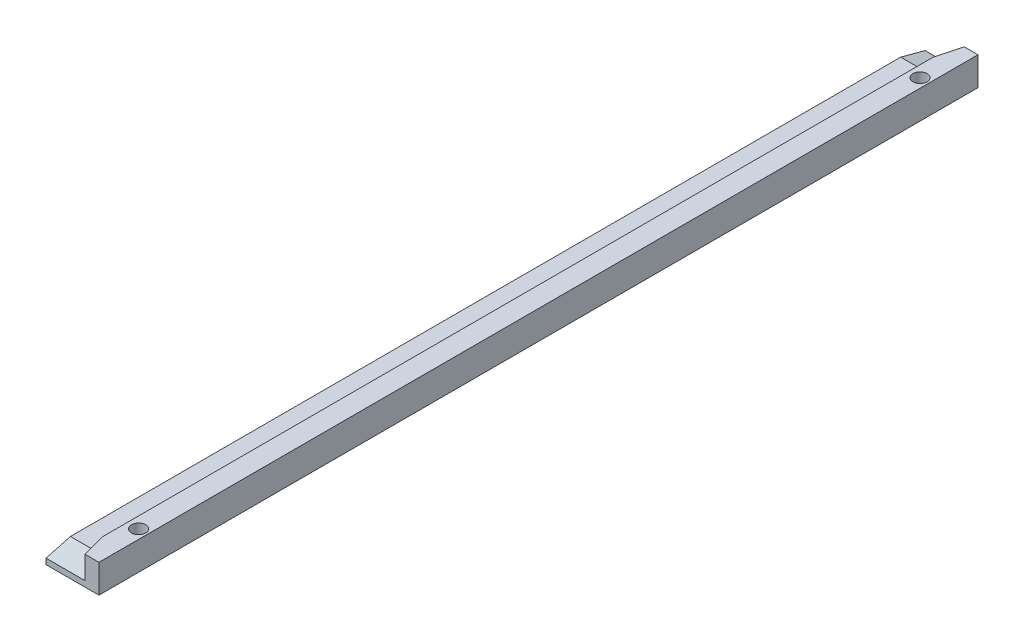
SolidWorks part; units mm, degrees
note: '?' marks a value the reader was unsure of.
material "6061 Alloy"
ref_plane "Front" through (0, 0, 0) normal (0, 0, 1) x (1, 0, 0)
ref_plane "Top" through (0, 0, 0) normal (0, 1, 0) x (1, 0, 0)
ref_plane "Right" through (0, 0, 0) normal (1, 0, 0) x (0, 0, -1)
ref_axis "X" through (-80.9, 0, 0) along (1, 0, 0)?
ref_axis "Y" through (0, 0, -80.9) along (0, 0, 1)?
ref_axis "Z" through (0, 50, 0) along (0, -1, 0)?
sketch "Sketch1" plane through (0, 0, 0) normal (0, 0, 1) x (1, 0, 0)
  line L0 (0, 0) -> (0, 22.225)
  line L1 (0, 0) -> (-28.448, 0)
  line L2 (-41.275, 9.525) -> (-15.875, 9.525)
  line L4 (-15.875, 9.525) -> (-15.875, 22.225)
  line L5 (-15.875, 22.225) -> (0, 22.225)
  line L7 (-41.275, 9.525) -> (-41.275, 0)
  line L8 (-41.275, 0) -> (-28.448, 0)
  dimension "D1" = 22.225
  dimension "D2" = 9.525
  dimension "D3" = 15.875
  dimension "D4" = 28.448
  dimension "D5" = 25.4
extrude "Extrude1" add sketch "Sketch1" against normal mid plane 685.8
chamfer "Chamfer1" distance 19.05 angle 15 2 edges at (-15.875, 15.875, 342.9) (-28.575, 9.525, 342.9)
chamfer "Chamfer3" distance 19.05 angle 15 2 edges at (-15.875, 15.875, -342.9) (-28.575, 9.525, -342.9)
hole_wizard "CBORE for 1/4 Socket Head Cap Screw1" positions "Sketch3" profile "Sketch2" counterbore size "1/4" standard "Ansi Inch" end condition through all
sketch "Sketch3" plane through (0, 22.225, 0) normal (0, 1, 0) x (-1, 0, 0)
  line L1 (0, -342.9) -> (0, 342.9) construction
  line L3 (0, -342.9) -> (10.7706, -342.9) construction
  line L4 (0, 342.9) -> (10.7706, 342.9) construction
  point P1 (7.112, 304.8)
  point P5 (7.112, -304.8)
  point P17 (5.3853, 342.9)
  dimension "D1" = 38.1
  dimension "D2" = 7.112
  dimension "D4" = 38.1
  dimension "D5" = 7.112
sketch "Sketch2" plane through (-7.112, 22.225, 304.8) normal (1, 0, 0) x (0, 0, 1)
  line L0 (0, 0) -> (0, 22.225)
  line L1 (0, 22.225) -> (3.3782, 22.225)
  line L3 (3.3782, 22.225) -> (3.3782, 16.51)
  line L4 (3.3782, 16.51) -> (5.5562, 16.51)
  line L5 (5.5562, 16.51) -> (5.5562, 0)
  line L7 (5.5562, 0) -> (0, 0)
  line L11 (0, -6.35) -> (0, 107.95) construction
  dimension "Thru Hole Dia." = 6.7564
  dimension "Thru Hole Depth" = 22.225
  dimension "C'Bore Dia." = 11.1125
  dimension "C'Bore Depth" = 16.51
hole_wizard "C (0.242) Diameter Hole1" positions "Sketch5" profile "Sketch4" hole size "C" standard "Ansi Inch" end condition through all
sketch "Sketch5" plane through (2.0772, 9.525, 2.747) normal (0, -1, 0) x (1, 0, 0)
  line L6 (-22.6512, -2.747) -> (-138.0041, -2.747) construction
  line L7 (-43.3522, -345.647) -> (-12.8478, -345.647) construction
  line L8 (-12.8478, 340.153) -> (-43.3522, 340.153) construction
  line L9 (-43.3522, -345.647) -> (-43.3522, 340.153) construction
  point P0 (-22.6512, 261.5254)
  point P1 (-22.6512, -267.0194)
  dimension "D1" = 78.6276
  dimension "D2" = 78.6276
  dimension "D3" = 20.701
sketch "Sketch4" plane through (-20.574, 9.525, 264.2724) normal (1, 0, 0) x (0, 0, 1)
  line L0 (0, 0) -> (0, 9.525)
  line L1 (0, 9.525) -> (3.0734, 9.525)
  line L2 (3.0734, 9.525) -> (3.0734, 0)
  line L5 (3.0734, 0) -> (0, 0)
  line L11 (0, -6.35) -> (0, 107.95) construction
  dimension "Thru Hole Dia." = 6.1468
  dimension "Thru Hole Depth" = 9.525
